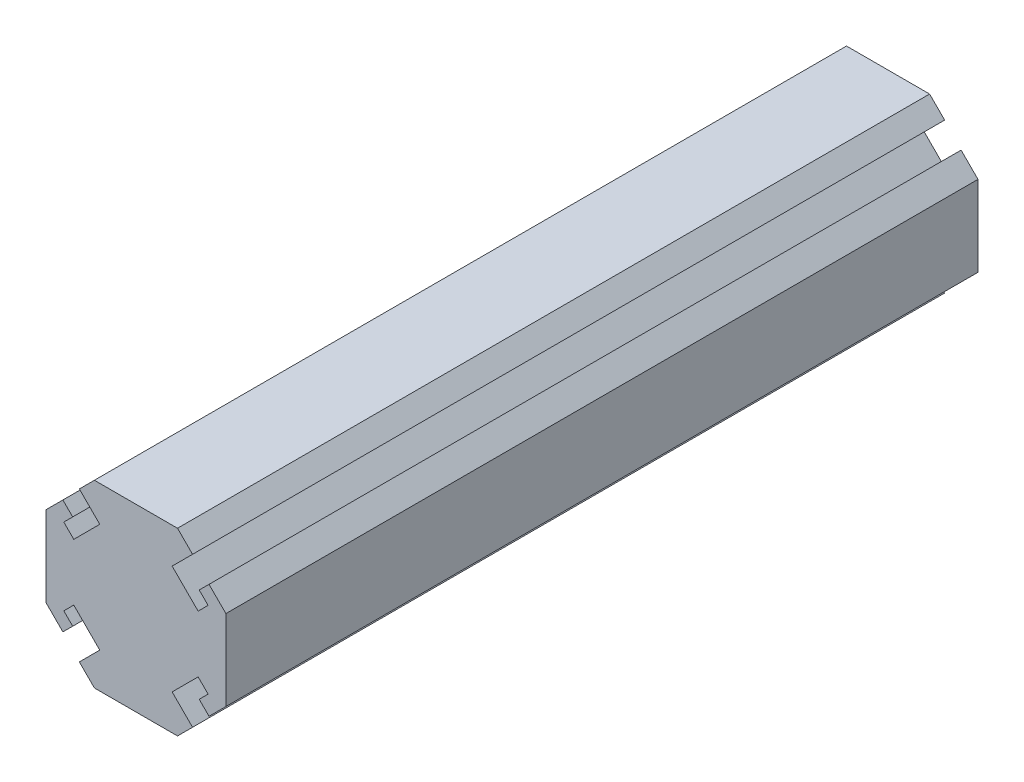
SolidWorks part; units mm, degrees
ref_plane "Спереди" through (0, 0, 0) normal (0, 0, 1) x (1, 0, 0)
ref_plane "Сверху" through (0, 0, 0) normal (0, 1, 0) x (1, 0, 0)
ref_plane "Справа" through (0, 0, 0) normal (1, 0, 0) x (0, 0, -1)
sketch "Эскиз1" plane through (0, 0, 0) normal (0, 0, 1) x (1, 0, 0)
  line L0 (-47.2719, 0) -> (56.8927, 0) construction
  line L1 (4.7944, 53.9243) -> (4.7944, -61.466) construction
  line L2 (-31.0859, 16.0554) -> (-31.0859, -16.0554)
  line L3 (-11.7832, -35.8817) -> (-17.7877, -29.8772)
  line L4 (-11.7832, -35.8817) -> (21.372, -35.8817)
  line L5 (-17.7877, -29.8772) -> (-9.6375, -21.727)
  line L6 (-9.6375, -21.727) -> (-20.0099, -11.3546)
  line L7 (-20.0099, -11.3546) -> (-23.9877, -15.3325)
  line L8 (-23.9877, -15.3325) -> (-20.4411, -18.879)
  line L9 (-31.0859, -16.0554) -> (-24.3517, -22.7896)
  line L10 (-24.3517, -22.7896) -> (-20.4411, -18.879)
  line L11 (-31.0859, 16.0554) -> (-24.3517, 22.7896)
  line L12 (-24.3517, 22.7896) -> (-20.4411, 18.879)
  line L13 (-23.9877, 15.3325) -> (-20.4411, 18.879)
  line L14 (-20.0099, 11.3546) -> (-23.9877, 15.3325)
  line L15 (-9.6375, 21.727) -> (-20.0099, 11.3546)
  line L16 (-17.7877, 29.8772) -> (-9.6375, 21.727)
  line L17 (-11.7832, 35.8817) -> (-17.7877, 29.8772)
  line L18 (-11.7832, 35.8817) -> (21.372, 35.8817)
  line L19 (21.372, 35.8817) -> (27.3764, 29.8772)
  line L20 (27.3764, 29.8772) -> (19.2262, 21.727)
  line L21 (19.2262, 21.727) -> (29.5986, 11.3546)
  line L22 (29.5986, 11.3546) -> (33.5765, 15.3325)
  line L23 (33.5765, 15.3325) -> (30.0299, 18.879)
  line L24 (33.9405, 22.7896) -> (30.0299, 18.879)
  line L25 (40.6747, 16.0554) -> (33.9405, 22.7896)
  line L26 (33.9405, -22.7896) -> (30.0299, -18.879)
  line L27 (40.6747, -16.0554) -> (33.9405, -22.7896)
  line L28 (33.5765, -15.3325) -> (30.0299, -18.879)
  line L29 (29.5986, -11.3546) -> (33.5765, -15.3325)
  line L30 (19.2262, -21.727) -> (29.5986, -11.3546)
  line L31 (27.3764, -29.8772) -> (19.2262, -21.727)
  line L32 (21.372, -35.8817) -> (27.3764, -29.8772)
  line L33 (40.6747, 16.0554) -> (40.6747, -16.0554)
  point P16 (-31.0859, 0)
  point P25 (4.7944, 35.8817)
  point P40 (4.7944, -35.8817)
extrude "Бобышка-Вытянуть1" add sketch "Эскиз1" against normal blind 300
